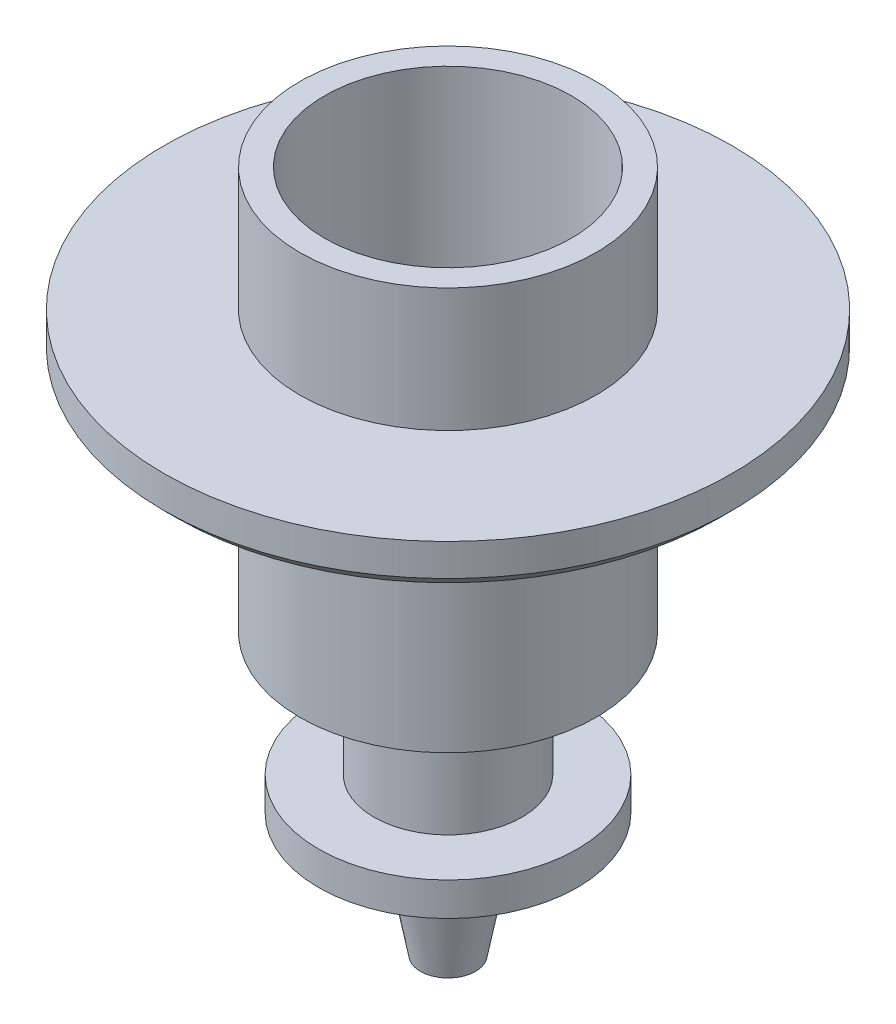
SolidWorks part; units mm, degrees
material "ABS"
ref_plane "Front Plane" through (0, 0, 0) normal (0, 0, 1) x (1, 0, 0)
ref_plane "Top Plane" through (0, 0, 0) normal (0, 1, 0) x (1, 0, 0)
ref_plane "Right Plane" through (0, 0, 0) normal (1, 0, 0) x (0, 0, -1)
sketch "Sketch1" plane through (0, 0, 0) normal (0, 0, 1) x (1, 0, 0)
  line L0 (0, 11.5286) -> (0, -15.4714) construction
  line L1 (-3, 11.5286) -> (-3, 9.0286)
  line L2 (-3, 9.0286) -> (-5.75, 9.0286)
  line L3 (-5.75, 9.0286) -> (-5.75, 8.3786)
  line L4 (-5.5, 8.1286) -> (-3, 8.1286)
  line L5 (-3, 8.1286) -> (-3, 3.3786)
  line L6 (-1.6263, 2.8786) -> (-1.5, 2.8786)
  line L7 (-1.5, 2.8786) -> (-1.5, 0.8786)
  line L8 (-1.5, 0.8786) -> (-2.6185, 0.8786)
  line L9 (-2.6185, 0.8786) -> (-2.6185, 0.2033)
  line L10 (-2.6185, 0.2033) -> (-1.0316, 0.2033)
  line L11 (-1.0316, 0.2033) -> (-0.5589, -2.2952)
  line L12 (-3, 11.5286) -> (0, 11.5286)
  line L13 (-0.5589, -2.2952) -> (0, -2.2952)
  line L14 (-3, 3.3786) -> (-1.6263, 2.8786)
  line L15 (-5.75, 8.3786) -> (-5.5, 8.1286)
  line L16 (0, 11.5286) -> (0, -2.2952)
  point P7 (-5.75, 8.1286)
  point P9 (-3, 2.8786)
  dimension "D1" = 3
  dimension "D2" = 0.9
  dimension "D3" = 2.75
  dimension "D4" = 2.75
  dimension "D5" = 2.5
  dimension "D6" = 5.25
  dimension "D7" = 2
  dimension "D8" = 0.5
  dimension "D9" = 70
  dimension "D10" = 0.25
  dimension "D11" = 45
revolve "Revolve1" add sketch "Sketch1" angle 360 about L0
sketch "Sketch2" plane through (0, 11.5286, 0) normal (0, 1, 0) x (1, 0, 0)
  circle A0 centre (0, 0) radius 2.5
  circle A1 centre (0, 0) radius 0.3
extrude "Cut-Extrude1" cut sketch "Sketch2" against normal through all contours A1
extrude "Cut-Extrude2" cut sketch "Sketch2<3>" against normal blind 7.5
sketch "Sketch2<3>" plane through (0, 11.5286, 0) normal (0, 1, 0) x (1, 0, 0) same geometry as "Sketch2"
